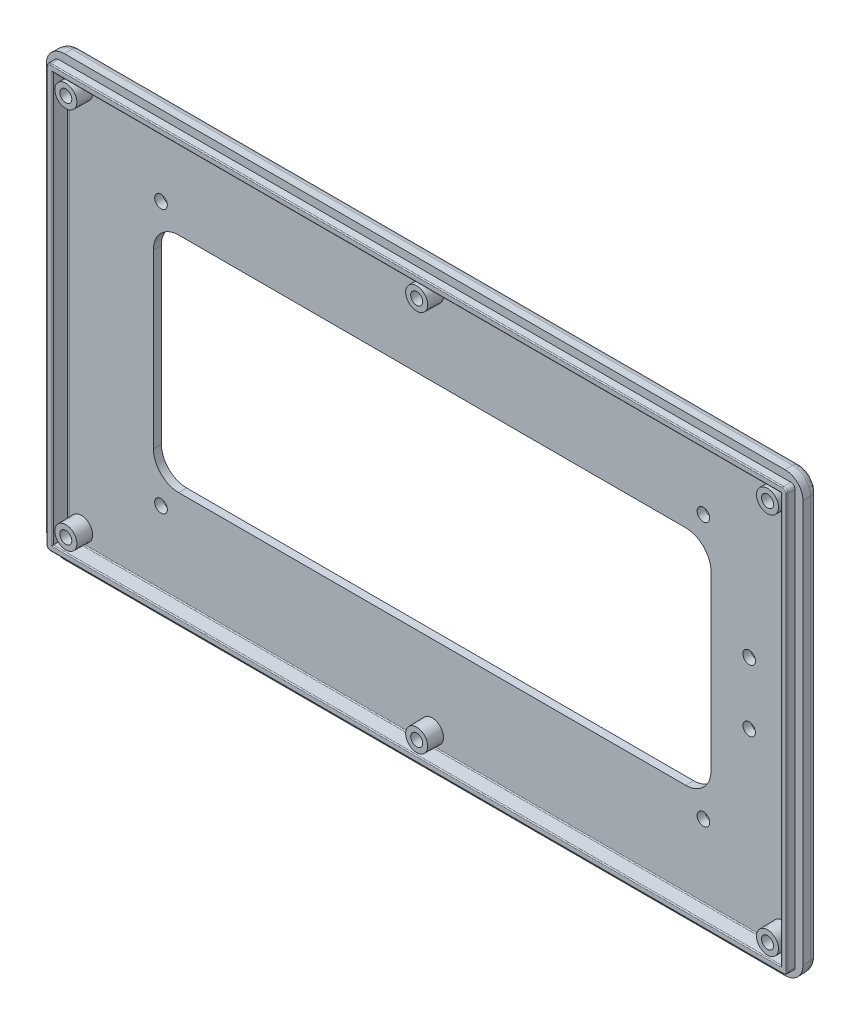
SolidWorks part; units mm, degrees
ref_plane "Front Plane" through (0, 0, 0) normal (0, 0, 1) x (1, 0, 0)
ref_plane "Top Plane" through (0, 0, 0) normal (0, 1, 0) x (1, 0, 0)
ref_plane "Right Plane" through (0, 0, 0) normal (1, 0, 0) x (0, 0, -1)
sketch "Sketch1" plane through (0, 0, 0) normal (0, 0, 1) x (1, 0, 0)
  line L0 (-95, -55) -> (95, -55)
  line L1 (95, -55) -> (95, 55)
  line L2 (95, 55) -> (-95, 55)
  line L3 (-95, 55) -> (-95, -55)
extrude "Boss-Extrude1" add sketch "Sketch1" against normal blind 3.9 draft 1
sketch "Sketch2" plane through (0, 0, 0) normal (0, 0, 1) x (1, 0, 0)
  line L0 (-93, 53) -> (93, 53)
  line L1 (93, 53) -> (93, -53)
  line L2 (93, -53) -> (-93, -53)
  line L3 (-93, -53) -> (-93, 53)
extrude "Boss-Extrude2" add sketch "Sketch2" along normal blind 2 draft 1
sketch "Sketch3" plane through (0, 0, 2) normal (0, 0, 1) x (1, 0, 0)
  line L0 (-91.4349, 51.4349) -> (-91.4349, -51.4349)
  line L1 (-91.4349, -51.4349) -> (91.4349, -51.4349)
  line L2 (91.4349, -51.4349) -> (91.4349, 51.4349)
  line L3 (91.4349, 51.4349) -> (-91.4349, 51.4349)
extrude "Cut-Extrude1" cut sketch "Sketch3" against normal blind 3.9 draft 1
ref_plane "Plane1" through (0, -48, 0) normal (0, 1, 0) x (1, 0, 0)
sketch "Sketch4" plane through (0, -48, 0) normal (0, 1, 0) x (1, 0, 0)
  line L0 (-85.2668, 1.9) -> (-88.1, 1.9)
  line L1 (-88.1, 1.9) -> (-88.1, -2)
  line L2 (-88.1, -2) -> (-85.3349, -2)
  line L3 (-85.3349, -2) -> (-85.2668, 1.9)
  line L4 (-88.1, 1.9) -> (-88.1, -2) construction
revolve "Revolve1" add sketch "Sketch4" angle 360 about L4 reverse direction yes
ref_plane "Plane2" through (0, 48, 0) normal (0, 1, 0) x (1, 0, 0)
sketch "Sketch5" plane through (0, 48, 0) normal (0, 1, 0) x (1, 0, 0)
  line L0 (2.8332, 1.9) -> (0, 1.9)
  line L1 (0, 1.9) -> (0, -2)
  line L2 (0, -2) -> (2.7651, -2)
  line L3 (2.7651, -2) -> (2.8332, 1.9)
  line L4 (0, 1.9) -> (0, -2) construction
revolve "Revolve2" add sketch "Sketch5" angle 360 about L4 reverse direction yes
sketch "Sketch6" plane through (0, -48, 0) normal (0, 1, 0) x (1, 0, 0)
  line L0 (90.9332, 1.9) -> (88.1, 1.9)
  line L1 (88.1, 1.9) -> (88.1, -2)
  line L2 (88.1, -2) -> (90.8651, -2)
  line L3 (90.8651, -2) -> (90.9332, 1.9)
  line L4 (88.1, 1.9) -> (88.1, -2) construction
revolve "Revolve3" add sketch "Sketch6" angle 360 about L4 reverse direction yes
sketch "Sketch7" plane through (0, 48, 0) normal (0, 1, 0) x (1, 0, 0)
  line L0 (90.9332, 1.9) -> (88.1, 1.9)
  line L1 (88.1, 1.9) -> (88.1, -2)
  line L2 (88.1, -2) -> (90.8651, -2)
  line L3 (90.8651, -2) -> (90.9332, 1.9)
  line L4 (88.1, 1.9) -> (88.1, -2) construction
revolve "Revolve4" add sketch "Sketch7" angle 360 about L4 reverse direction yes
sketch "Sketch8" plane through (0, -48, 0) normal (0, 1, 0) x (1, 0, 0)
  line L0 (2.8332, 1.9) -> (0, 1.9)
  line L1 (0, 1.9) -> (0, -2)
  line L2 (0, -2) -> (2.7651, -2)
  line L3 (2.7651, -2) -> (2.8332, 1.9)
  line L4 (0, 1.9) -> (0, -2) construction
revolve "Revolve5" add sketch "Sketch8" angle 360 about L4 reverse direction yes
sketch "Sketch9" plane through (0, 48, 0) normal (0, 1, 0) x (1, 0, 0)
  line L0 (-85.2668, 1.9) -> (-88.1, 1.9)
  line L1 (-88.1, 1.9) -> (-88.1, -2)
  line L2 (-88.1, -2) -> (-85.3349, -2)
  line L3 (-85.3349, -2) -> (-85.2668, 1.9)
  line L4 (-88.1, 1.9) -> (-88.1, -2) construction
revolve "Revolve6" add sketch "Sketch9" angle 360 about L4 reverse direction yes
hole_wizard "CSK for M2.5 Flat Head Machine Screw1" positions "Sketch11" profile "Sketch10" countersink size "M2.5" standard "ANSI Metric"
sketch "Sketch11" plane through (0, 0, -3.9) normal (0, 0, -1) x (-1, 0, 0)
  point P0 (88.1, 48)
  point P1 (0, -48)
  point P2 (-88.1, 48)
  point P3 (-88.1, -48)
  point P4 (0, 48)
  point P5 (88.1, -48)
sketch "Sketch10" plane through (-88.1, 48, -3.9) normal (1, 0, 0) x (0, 1, 0)
  line L0 (0, 0) -> (0, 5.9)
  line L1 (0, 5.9) -> (1.5, 5.9)
  line L2 (1.5, 5.9) -> (1.5, 1.8)
  line L3 (1.5, 1.8) -> (2.8, 0.5)
  line L4 (2.8, 0.5) -> (2.8, 0)
  line L6 (2.8, 0) -> (0, 0)
  line L7 (-1.5, 1.8) -> (-2.8, 0.5) construction
  line L11 (0, -6.35) -> (0, 107.95) construction
  dimension "Thru Hole Dia." = 3
  dimension "Thru Hole Depth" = 5.9
  dimension "C'Sink Dia." = 5.6
  dimension "C'Sink Angle" = 90
  dimension "Head Clearance" = 0.5
fillet "Fillet1" radius 1 4 edges at (92.9825, 52.9825, 1) (-92.9825, 52.9825, 1) (-92.9825, -52.9825, 1) (92.9825, -52.9825, 1) tangent propagation no
fillet "Fillet2" radius 4.5 4 edges at (94.966, 54.966, -1.95) (94.966, -54.966, -1.95) (-94.966, 54.966, -1.95) (-94.966, -54.966, -1.95) tangent propagation no
fillet "Fillet3" radius 0.25 16 edges at (92.6723, 52.6723, 2) (0, 52.9651, 2) (92.9651, 0, 2) (-92.6723, 52.6723, 2) (92.6723, -52.6723, 2) (-92.9651, 0, 2) (0, -52.9651, 2) (-92.6723, -52.6723, 2) (-91.4349, 0, 2) (0, -51.4349, 2) (0, 51.4349, 2) (91.4349, 0, 2) (0, 51.3668, -1.9) (-91.3668, 0, -1.9) (91.3668, 0, -1.9) (0, -51.3668, -1.9)
fillet "Fillet4" radius 2 8 edges at (0, 54.9319, -3.9) (93.6142, 53.6142, -3.9) (-93.6142, 53.6142, -3.9) (94.9319, 0, -3.9) (-94.9319, 0, -3.9) (93.6142, -53.6142, -3.9) (-93.6142, -53.6142, -3.9) (0, -54.9319, -3.9) tangent propagation no
sketch "Sketch12" plane through (0, 0, -3.9) normal (0, 0, -1) x (-1, 0, 0)
  line L1 (-63.65, -28) -> (63.65, -28)
  line L2 (-70, -21.65) -> (-70, 21.65)
  line L3 (-63.65, 28) -> (63.65, 28)
  line L4 (70, -21.65) -> (70, 21.65)
  line L5 (-70, -28) -> (70, 28) construction
  line L6 (-70, 28) -> (70, -28) construction
  arc A0 (-63.65, -28) -> (-70, -21.65) centre (-63.65, -21.65) cw
  arc A1 (63.65, -28) -> (70, -21.65) centre (63.65, -21.65) ccw
  arc A2 (63.65, 28) -> (70, 21.65) centre (63.65, 21.65) cw
  arc A3 (-70, 21.65) -> (-63.65, 28) centre (-63.65, 21.65) cw
  circle A4 centre (-68.1, 33.1) radius 1.5875
  circle A5 centre (68.1, 33.1) radius 1.5875
  circle A6 centre (68.1, -33.1) radius 1.5875
  circle A7 centre (-68.1, -33.1) radius 1.5875
  point P0 (0, 0)
  dimension "D3" = 6.35
  dimension "D4" = 3.175
  dimension "D5" = 3.175
  dimension "D6" = 3.175
  dimension "D7" = 3.175
  dimension "D1" = 56
  dimension "D2" = 140
extrude "Cut-Extrude2" cut sketch "Sketch12" against normal up to next
sketch "Sketch14" plane through (0, 0, -1.9) normal (0, 0, 1) x (1, 0, 0)
  circle A0 centre (79.6015, 7.7894) radius 1.5755
  circle A1 centre (79.6015, -7.7681) radius 1.5555
extrude "Cut-Extrude3" cut sketch "Sketch14" against normal up to next
